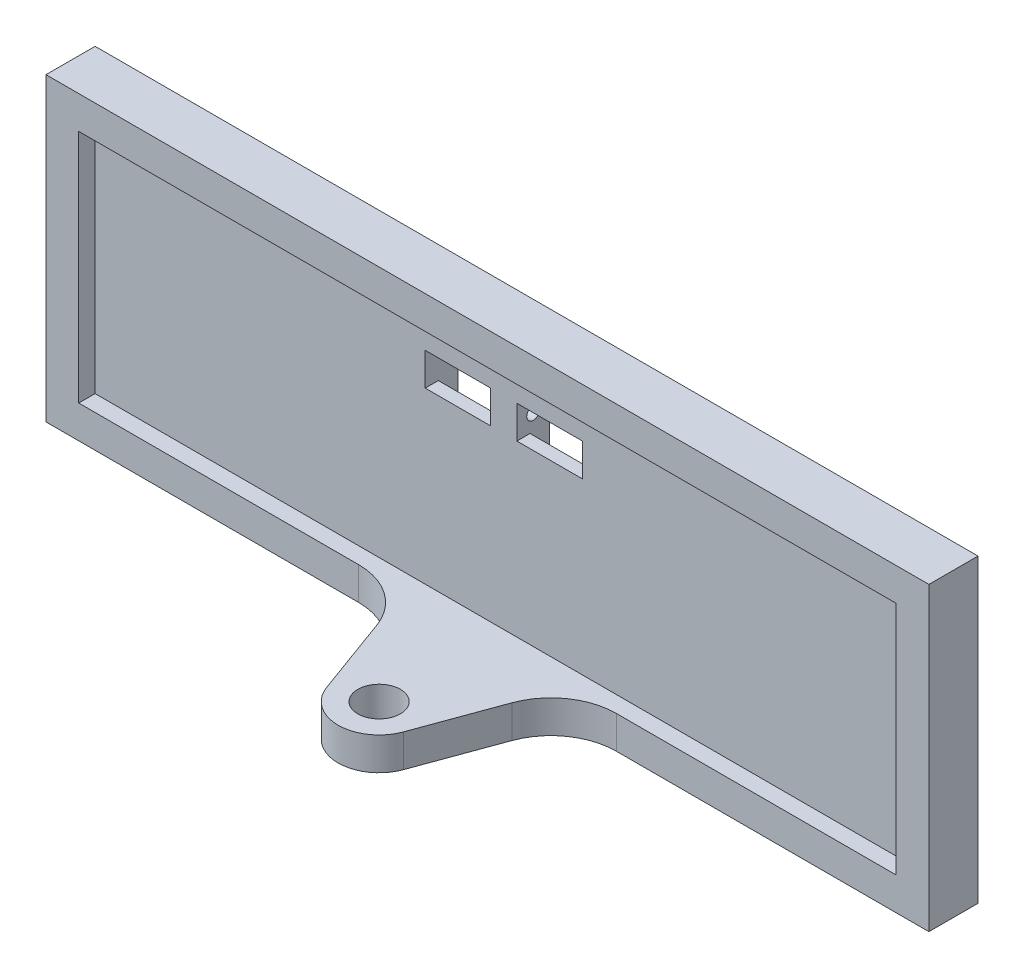
SolidWorks part; units mm, degrees
ref_plane "Front Plane" through (0, 0, 0) normal (0, 0, 1) x (1, 0, 0)
ref_plane "Top Plane" through (0, 0, 0) normal (0, 1, 0) x (1, 0, 0)
ref_plane "Right Plane" through (0, 0, 0) normal (1, 0, 0) x (0, 0, -1)
sketch "Sketch1" plane through (0, 0, 0) normal (0, 0, 1) x (1, 0, 0)
  line L0 (-62.415, 17.965) -> (62.415, 17.965)
  line L1 (-61.915, 17.465) -> (61.915, 17.465) construction
  line L2 (-61.915, 17.465) -> (-61.915, -17.465) construction
  line L3 (-61.915, -17.465) -> (61.915, -17.465) construction
  line L4 (61.915, 17.465) -> (61.915, -17.465) construction
  line L5 (-61.915, 17.465) -> (61.915, -17.465) construction
  line L6 (-61.915, -17.465) -> (61.915, 17.465) construction
  line L7 (62.415, 17.965) -> (62.415, -17.965)
  line L8 (-62.415, -17.965) -> (62.415, -17.965)
  line L9 (-62.415, 17.965) -> (-62.415, -17.965)
  line L10 (-67.415, 22.965) -> (67.415, 22.965)
  line L11 (67.415, 22.965) -> (67.415, -22.965)
  line L12 (-67.415, -22.965) -> (67.415, -22.965)
  line L13 (-67.415, 22.965) -> (-67.415, -22.965)
  point P0 (0, 0)
  dimension "D2" = 34.93
  dimension "D1" = 123.83
  dimension "D3" = 0.5
  dimension "D4" = 5
extrude "Boss-Extrude1" add sketch "Sketch1" along normal mid plane 5 contours L10 L13 L12 L11 L9 L0 L7 L8 | L0 L9 L8 L7 | L0 L7 L8 L9 | L10 L11 L12 L13 region at (0, 0, 0) region at (0, 21.5406, 0)
extrude "Boss-Extrude2" add sketch "Sketch1<3>" along normal mid plane 5 from surface starting at face at (0, 0, 2.5)
sketch "Sketch1<3>" plane through (0, 0, 0) normal (0, 0, 1) x (1, 0, 0) same geometry as "Sketch1"
sketch "Sketch2" plane through (0, -22.965, 0) normal (0, -1, 0) x (1, 0, 0)
  line L0 (-67.415, 2.5) -> (67.415, 2.5) construction
  line L1 (-67.415, 5) -> (-67.415, -2.5) construction
  line L2 (67.415, 5) -> (67.415, -2.5) construction
  line L5 (67.415, 5) -> (-67.415, 5) construction
  line L7 (0, 2.5) -> (0, 21.55) construction
  line L8 (-5.8705, 23.6946) -> (-12.7, 5)
  line L9 (-12.7, 5) -> (12.7, 5)
  line L10 (5.8705, 23.6946) -> (12.7, 5)
  circle A0 centre (0, 21.55) radius 3.25
  circle A1 centre (0, 21.55) radius 6.25
  point P18 (0, 5)
  line M10 (67.415, 5) -> (-67.415, 5)
  dimension "D3" = 6.5
  dimension "D1" = 2.5
  dimension "D2" = 19.05
  dimension "D5" = 12.7
  dimension "D4" = 3
extrude "Boss-Extrude3" add sketch "Sketch2" against normal up to surface (5 mm away) contours A1 L8 L10 M10 | A1 A0 region at (0, -22.965, 10.9023) region at (0, -22.965, 27.6232) up to face at (0, -17.965, 3.75)
fillet "Fillet1" radius 10 2 edges at (-12.7, -20.465, 5) (12.7, -20.465, 5)
sketch "Sketch5" plane through (0, 0, -2.5) normal (0, 0, -1) x (-1, 0, 0)
  line L0 (0, 22.965) -> (0, -22.965) construction
  line L1 (67.415, 22.965) -> (-67.415, 22.965) construction
  line L2 (67.415, -22.965) -> (-67.415, -22.965) construction
  line L3 (12, 7.965) -> (2, 7.965)
  line L4 (-12, 12.965) -> (-2, 12.965)
  line L5 (-12, 12.965) -> (-12, 7.965)
  line L6 (-12, 7.965) -> (-2, 7.965)
  line L7 (-2, 12.965) -> (-2, 7.965)
  line L8 (-12, 12.965) -> (-2, 7.965) construction
  line L9 (-12, 7.965) -> (-2, 12.965) construction
  line L10 (2, 12.965) -> (2, 7.965)
  line L11 (12, 12.965) -> (2, 12.965)
  line L12 (12, 12.965) -> (12, 7.965)
  point P6 (-7, 10.465)
  dimension "D1" = 5
  dimension "D2" = 10
  dimension "D3" = 2
  dimension "D4" = 10
extrude "Cut-Extrude4" cut sketch "Sketch5" against normal through all both and the other way through all
sketch "Sketch6" plane through (-2, 0, 0) normal (-1, 0, 0) x (0, 0, 1)
  line L0 (2.5, 12.965) -> (-2.5, 7.965) construction
  line L4 (-2.5, 7.965) -> (2.5, 7.965)
  line L5 (2.5, 7.965) -> (2.5, 12.965)
  line L6 (2.5, 12.965) -> (-2.5, 12.965)
  line L7 (-2.5, 12.965) -> (-2.5, 7.965)
  line L8 (-2.5, 7.965) -> (2.5, 7.965) construction
  line L9 (2.5, 7.965) -> (2.5, 12.965) construction
  line L10 (2.5, 12.965) -> (-2.5, 12.965) construction
  line L11 (-2.5, 12.965) -> (-2.5, 7.965) construction
  circle A0 centre (0, 10.465) radius 1
  dimension "D2" = 2
  dimension "D1" = 0
extrude "Cut-Extrude5" cut sketch "Sketch6" against normal up to next from surface starting at face at (-2, 10.465, 0)
chamfer "Chamfer1" distance 3 angle 45 4 edges at (-7, 12.965, -2.5) (-7, 7.965, -2.5) (7, 7.965, -2.5) (7, 12.965, -2.5)
equation "\"CamWidth\"= 123.83"
equation "\"CamHeight\"= 34.93"
equation "\"D2@Sketch1\"=\"CamHeight\""
equation "\"D1@Sketch1\"=\"CamWidth\""
equation "\"CamWraparound\"= 5"
equation "\"CamOffset\"= 0.5"
equation "\"D3@Sketch1\"=\"CamOffset\""
